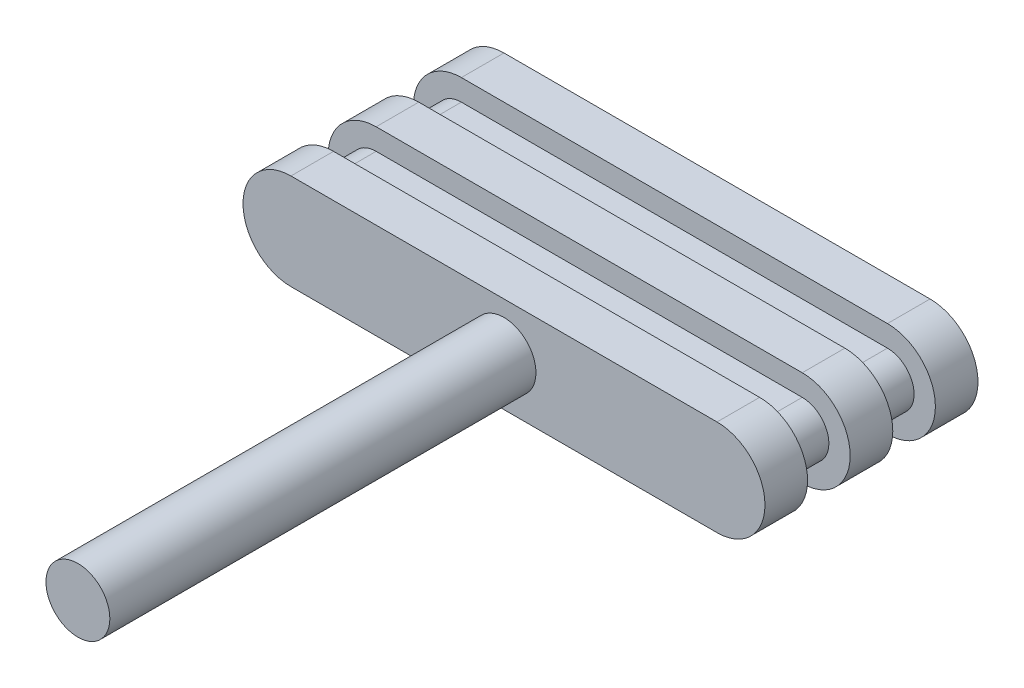
SolidWorks part; units mm, degrees
ref_plane "Front Plane" through (0, 0, 0) normal (0, 0, 1) x (1, 0, 0)
ref_plane "Top Plane" through (0, 0, 0) normal (0, 1, 0) x (1, 0, 0)
ref_plane "Right Plane" through (0, 0, 0) normal (1, 0, 0) x (0, 0, -1)
sketch "Sketch1" plane through (0, 0, 0) normal (0, 0, 1) x (1, 0, 0)
  line L0 (0, 2.25) -> (-10, 2.25)
  line L5 (-10, -2.25) -> (0, -2.25)
  line L6 (0, -2.25) -> (10, -2.25)
  line L11 (10, 2.25) -> (0, 2.25)
  line L12 (0, 1.25) -> (-10, 1.25)
  line L13 (-10, -1.25) -> (0, -1.25)
  line L14 (0, -1.25) -> (10, -1.25)
  line L15 (10, 1.25) -> (0, 1.25)
  arc A0 (-10, 2.25) -> (-10, -2.25) centre (-10, 0) ccw
  arc A1 (10, -2.25) -> (10, 2.25) centre (10, 0) ccw
  arc A2 (-10, 1.25) -> (-10, -1.25) centre (-10, 0) ccw
  arc A3 (10, -1.25) -> (10, 1.25) centre (10, 0) ccw
  dimension "D3" = 2.25
  dimension "D1" = 1
  dimension "D2" = 20
extrude "Boss-Extrude1" add sketch "Sketch1" along normal mid plane 10 contours A0 | L14 A3 L15 L12 A2 L13 region at (5, 2.0009, 0) region at (0, 0, 0)
sketch "Sketch4" plane through (0, 0, 5) normal (0, 0, 1) x (1, 0, 0)
  circle A0 centre (0, 0) radius 1.5
  dimension "D1" = 3
extrude "Boss-Extrude3" add sketch "Sketch4" along normal blind 20
extrude "Cut-Extrude2" cut sketch "Sketch1<4>" against normal mid plane 2 from offset 2
sketch "Sketch1<4>" plane through (0, 0, 0) normal (0, 0, 1) x (1, 0, 0) same geometry as "Sketch1"
extrude "Cut-Extrude4" cut sketch "Sketch1<6>" against normal mid plane 2 from offset 2 offset against normal yes
sketch "Sketch1<6>" plane through (0, 0, 0) normal (0, 0, 1) x (1, 0, 0) same geometry as "Sketch1"
